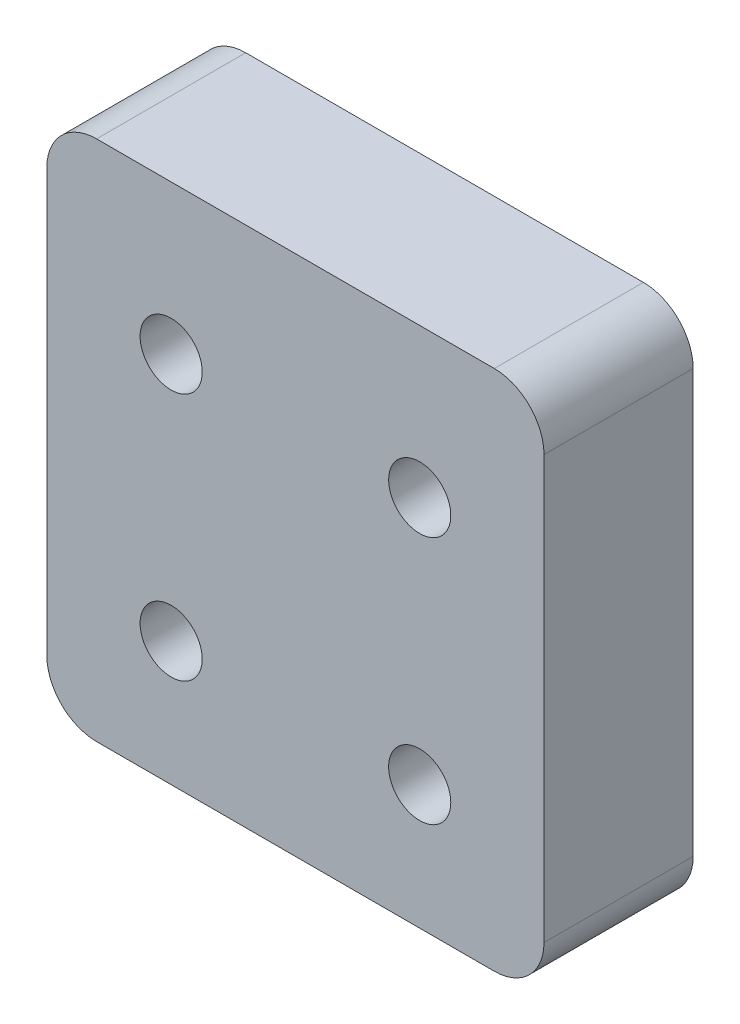
SolidWorks part; units mm, degrees
ref_plane "Front" through (0, 0, 0) normal (0, 0, 1) x (1, 0, 0)
ref_plane "Top" through (0, 0, 0) normal (0, 1, 0) x (1, 0, 0)
ref_plane "Right" through (0, 0, 0) normal (1, 0, 0) x (0, 0, -1)
sketch "Esquisse1" plane through (0, 0, 0) normal (0, 0, 1) x (1, 0, 0)
  line L1 (0, 0) -> (40, 0)
  line L2 (0, 0) -> (0, 42)
  line L3 (0, 42) -> (40, 42)
  line L4 (40, 0) -> (40, 42)
  dimension "D1" = 42
  dimension "D2" = 40
extrude "Boss.-Extru.1" add sketch "Esquisse1" along normal blind 12
sketch "Esquisse2" plane through (0, 0, 12) normal (0, 0, 1) x (1, 0, 0)
  line L0 (20, 42) -> (20, 0) construction
  line L1 (40, 42) -> (0, 42) construction
  line L2 (0, 0) -> (40, 0) construction
  line L3 (0, 20) -> (40, 20) construction
  line L4 (0, 42) -> (0, 0) construction
  line L5 (40, 0) -> (40, 42) construction
  circle A0 centre (10, 30) radius 2.5
  circle A1 centre (10, 10) radius 2.5
  circle A2 centre (30, 10) radius 2.5
  circle A3 centre (30, 30) radius 2.5
  dimension "D1" = 5
  dimension "D2" = 20
  dimension "D3" = 20
  dimension "D4" = 20
extrude "Enlèv. mat.-Extru.1" cut sketch "Esquisse2" against normal through all
fillet "Congé1" radius 4 4 edges at (40, 42, 6) (40, 0, 6) (0, 0, 6) (0, 42, 6)
